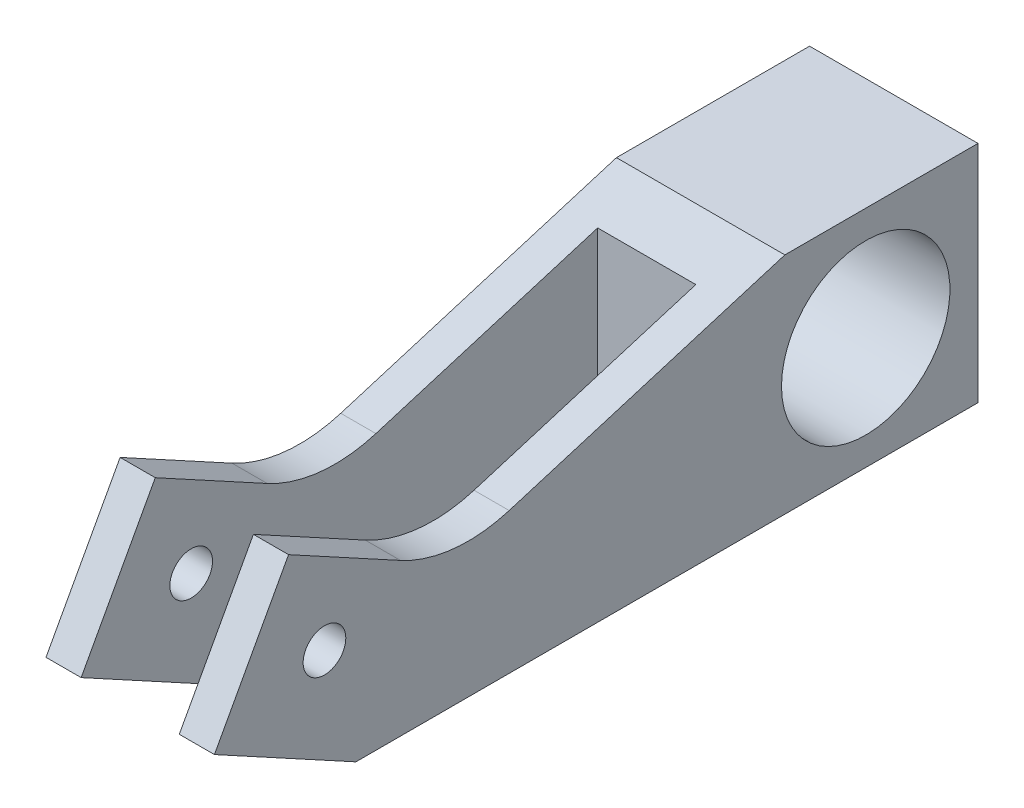
SolidWorks part; units mm, degrees
ref_plane "Front Plane" through (0, 0, 0) normal (0, 0, 1) x (1, 0, 0)
ref_plane "Top Plane" through (0, 0, 0) normal (0, 1, 0) x (1, 0, 0)
ref_plane "Right Plane" through (0, 0, 0) normal (1, 0, 0) x (0, 0, -1)
sketch "Sketch1" plane through (0, 0, 0) normal (1, 0, 0) x (0, 0, -1)
  line L0 (0, 0) -> (70.358, 0)
  line L1 (70.358, 0) -> (70.358, 25.4)
  line L2 (70.358, 25.4) -> (48.514, 25.4)
  line L3 (48.514, 25.4) -> (17.3329, 15.9511)
  line L4 (5.039, 17.2122) -> (-7.62, 24.106)
  line L5 (-7.62, 24.106) -> (-16.002, 8.7144)
  line L6 (-16.002, 8.7144) -> (0, 0)
  line L7 (70.358, 12.7) -> (-13.8315, 12.7) construction
  line L8 (42.418, 23.5527) -> (42.418, 0)
  circle A0 centre (57.658, 12.7) radius 9.525
  circle A1 centre (-3.556, 12.7) radius 2.413
  arc A2 (17.3329, 15.9511) -> (5.039, 17.2122) centre (12.6922, 31.2654) cw
  point P18 (10.922, 14.0084)
  dimension "D7" = 19.05
  dimension "D9" = 4.826
  dimension "D13" = 16.002
  dimension "D1" = 70.358
  dimension "D2" = 25.4
  dimension "D3" = 18.542
  dimension "D4" = 17.526
  dimension "D5" = 59.436
  dimension "D6" = 16.002
  dimension "D8" = 12.7
  dimension "D10" = 61.214
  dimension "D11" = 21.844
  dimension "D12" = 27.94
extrude "Boss-Extrude1" add sketch "Sketch1" along normal mid plane 19.05 contours L7 L1 L2 L3 L8 A0 | L1 L7 A0 L8 L0 region at (0, 6.35, -42.7249) region at (0, 18.1264, -42.7249)
extrude "Boss-Extrude2" add sketch "Sketch1<4>" against normal blind 3.9751 from vertex contours L7 L8 L3 A2 L4 L5 A1 | L8 L7 A1 L5 L6 L0 region at (0, 6.6077, -16.1549) region at (0, 13.2739, -20.6375) starting at point (9.525, 23.5527, -42.418)
sketch "Sketch1<4>" plane through (0, 0, 0) normal (1, 0, 0) x (0, 0, -1) same geometry as "Sketch1"
extrude "Boss-Extrude3" add sketch "Sketch1<5>" along normal blind 3.9751 from vertex contours L7 L8 L3 A2 L4 L5 A1 | L8 L7 A1 L5 L6 L0 region at (0, 6.6077, -16.1549) region at (0, 13.2739, -20.6375) starting at point (-9.525, 23.5527, -42.418)
sketch "Sketch1<5>" plane through (0, 0, 0) normal (1, 0, 0) x (0, 0, -1) same geometry as "Sketch1"
